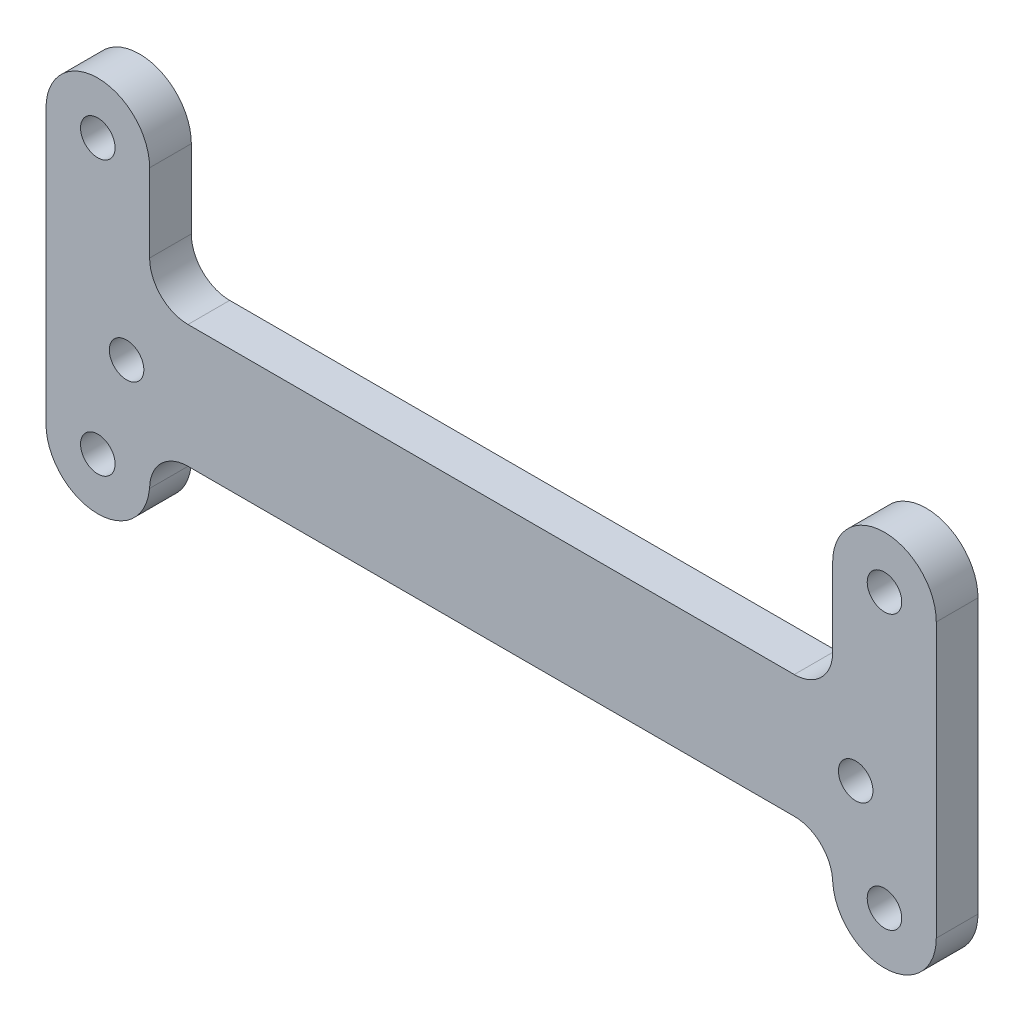
SolidWorks part; units mm, degrees
material "Acrylic (Medium-high impact)"
ref_plane "Front Plane" through (0, 0, 0) normal (0, 0, 1) x (1, 0, 0)
ref_plane "Top Plane" through (0, 0, 0) normal (0, 1, 0) x (1, 0, 0)
ref_plane "Right Plane" through (0, 0, 0) normal (1, 0, 0) x (0, 0, -1)
sketch "Sketch2" plane through (0, 0, 73.0838) normal (0, 0, -1) x (-1, 0, 0)
  line L2 (-47.5, -8) -> (47.5, -8)
  line L3 (47.5, 8) -> (-47.5, 8)
  line L4 (-39.5, -8) -> (39.5, -8)
  line L5 (39.5, 8) -> (-39.5, 8)
  line L6 (58, 23.184) -> (58, -12.4964)
  line L7 (-58, -12.4964) -> (-58, 23.184)
  line L8 (44.5, -12.4964) -> (44.5, -13)
  line L9 (-44.5248, -13.0739) -> (-44.4817, -12.5722)
  line L10 (-47.5, -8) -> (47.5, -8) construction
  line L11 (44.5, 23.184) -> (44.5, 13)
  line L12 (-44.5, 23.184) -> (-44.5, 13)
  circle A0 centre (47.5, 0) radius 2.25 construction
  circle A1 centre (-47.5, 0) radius 2.25 construction
  arc A2 (-47.5, 8) -> (-47.5, -8) centre (-47.5, 0) ccw
  arc A3 (47.5, -8) -> (47.5, 8) centre (47.5, 0) ccw
  circle A6 centre (47.5, 0) radius 2.25
  circle A7 centre (-47.5, 0) radius 2.25
  arc A8 (44.5, -12.4964) -> (58, -12.4964) centre (51.25, -12.4964) ccw
  arc A9 (58, 23.184) -> (44.5, 23.184) centre (51.25, 23.184) ccw
  arc A10 (-44.5, 23.184) -> (-58, 23.184) centre (-51.25, 23.184) ccw
  arc A11 (-58, -12.4964) -> (-44.5248, -13.0739) centre (-51.25, -12.4964) ccw
  circle A12 centre (51.25, 23.184) radius 2.25 construction
  circle A13 centre (51.25, -12.4964) radius 2.25 construction
  circle A14 centre (-51.25, -12.4964) radius 2.25 construction
  circle A15 centre (-51.25, 23.184) radius 2.25 construction
  arc A18 (53.7502, -32.8621) -> (-53.7502, -32.8621) centre (0, 0) ccw construction
  arc A19 (-44.5, 13) -> (-39.5, 8) centre (-39.5, 13) ccw
  arc A20 (-44.4817, -12.5722) -> (-39.5, -8) centre (-39.5, -13) cw
  arc A21 (44.5, -13) -> (39.5, -8) centre (39.5, -13) ccw
  arc A22 (44.5, 13) -> (39.5, 8) centre (39.5, 13) cw
  circle A23 centre (51.25, 23.184) radius 2.25
  circle A24 centre (51.25, -12.4964) radius 2.25
  circle A25 centre (-51.25, -12.4964) radius 2.25
  circle A26 centre (-51.25, 23.184) radius 2.25
  point P53 (44.5, -8)
  dimension "D2" = 5
  dimension "D1" = 0
extrude "Boss-Extrude1" add sketch "Sketch2" along normal blind 5.4356
